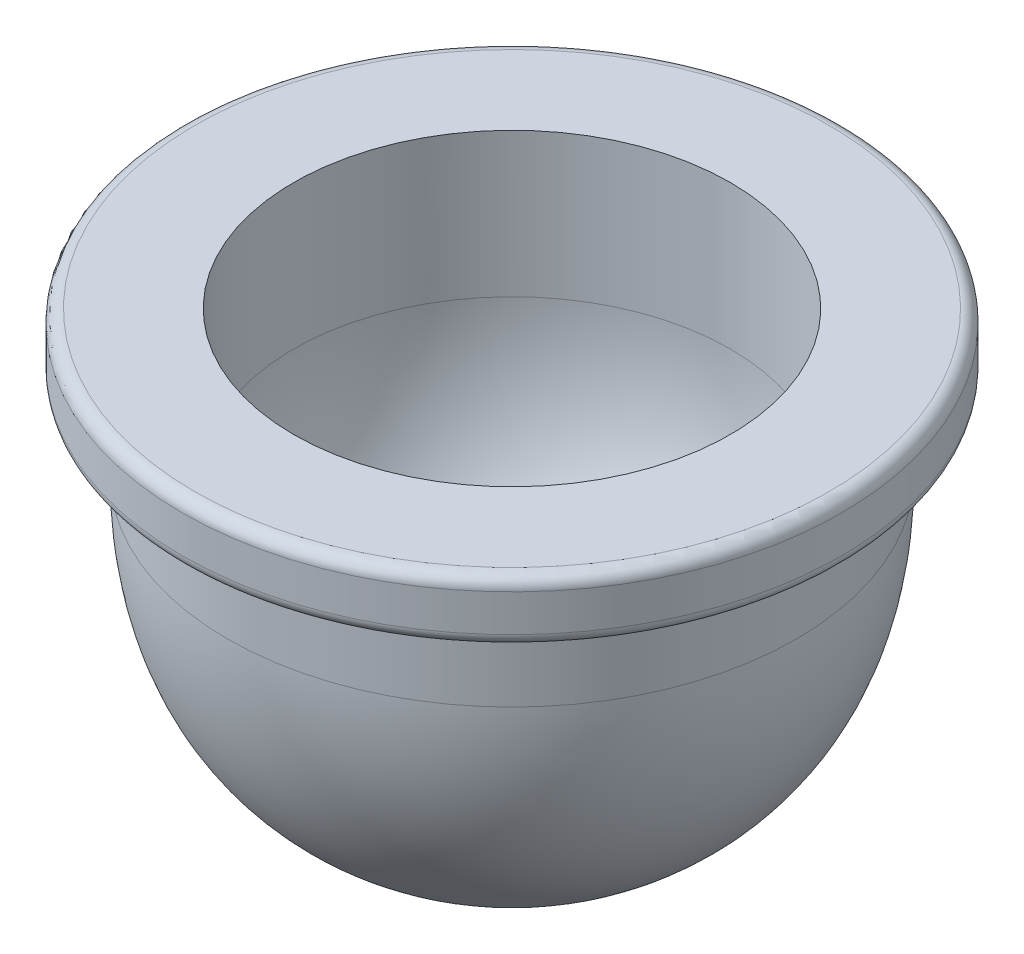
SolidWorks part; units mm, degrees
material "BUTYL"
ref_plane "Front Plane" through (0, 0, 0) normal (0, 0, 1) x (1, 0, 0)
ref_plane "Top Plane" through (0, 0, 0) normal (0, 1, 0) x (1, 0, 0)
ref_plane "Right Plane" through (0, 0, 0) normal (1, 0, 0) x (0, 0, -1)
sketch "Sketch1" plane through (0, 0, 0) normal (0, 0, 1) x (1, 0, 0)
  line L0 (-3, -11) -> (0, -11) construction
  line L1 (0, -11) -> (0, 0) construction
  line L2 (0, 0) -> (6.9, 0) construction
  line L3 (6.9, -1.5) -> (6.9, -3.5)
  line L4 (5.3, 0) -> (5.3, -3.5)
  line L5 (5.3, 0) -> (8, 0)
  line L6 (8, 0) -> (8, -1.5)
  line L7 (8, -1.5) -> (6.9, -1.5)
  line L8 (6.9, 0) -> (6.9, -3.5) construction
  line L9 (0, -9.4) -> (0, -11)
  spline S0 degree 3 poles (6.9, -3.5) (6.9, -8.6427) (3.3971, -11) (0, -11) knots 0 0 0 0 1 1 1 1
  spline S1 degree 1 poles (5.3, -3.5) (0, -9.4) knots 0 0 1 1 construction
  spline S2 degree 3 poles (5.3, -3.5) (5.3, -3.7639) (5.2765, -4.3085) (5.1458, -5.2569) (4.8444, -6.2836) (4.3128, -7.2665) (3.4204, -8.3064) (2.0032, -9.1661) (0.6606, -9.4) (0, -9.4) knots 0 0 0 0 0.0625 0.125 0.25 0.375 0.5 0.75 1 1 1 1
  dimension "D1" = 3
  dimension "D2" = 11
  dimension "D3" = 6.9
  dimension "D4" = 3.5
  dimension "D6" = 8
  dimension "D7" = 1.5
  dimension "D5" = 3.5
  dimension "D8" = 1.6
revolve "Revolve2" add sketch "Sketch1" angle 360 about L1
fillet "Fillet2" radius 0.3 2 edges at (0, -1.5, -8) (0, 0, -8)
